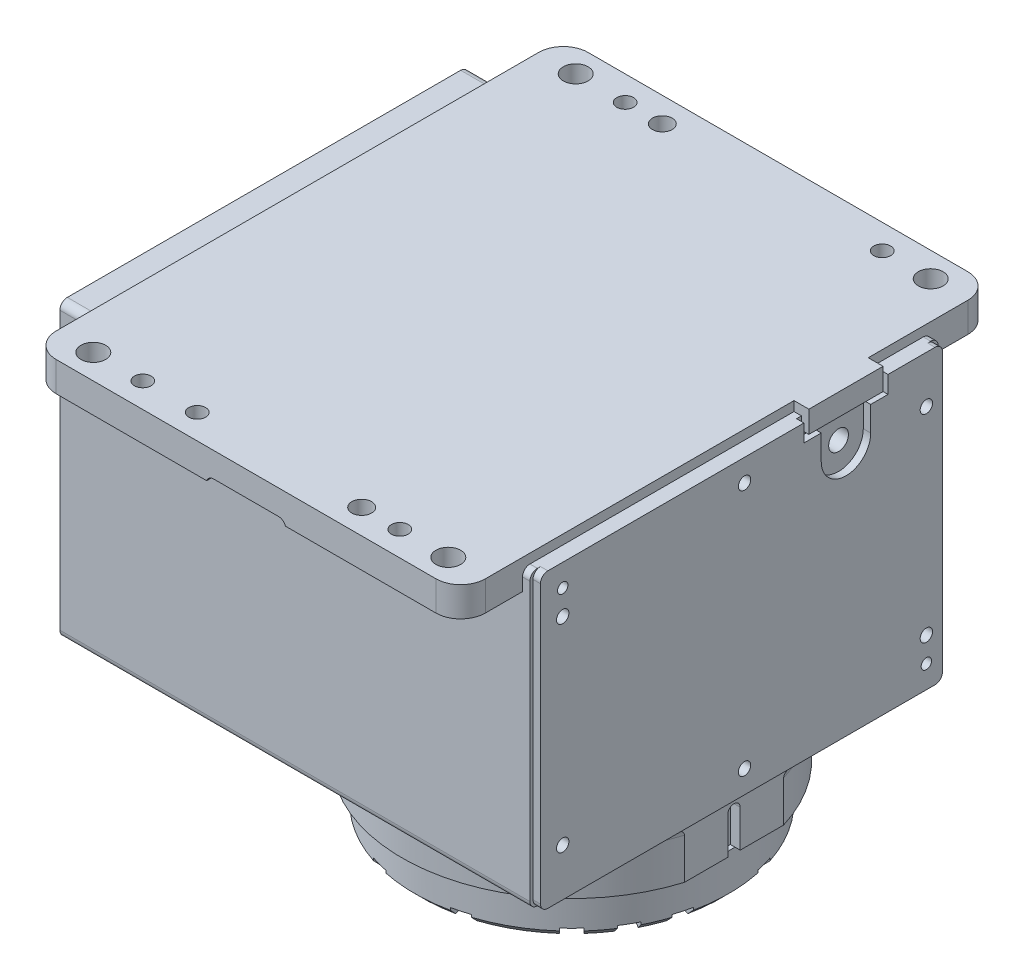
SolidWorks part; units mm, degrees
material "鋳合金鋼"
ref_plane "正面" through (0, 0, 0) normal (0, 0, 1) x (1, 0, 0)
ref_plane "平面" through (0, 0, 0) normal (0, 1, 0) x (1, 0, 0)
ref_plane "右側面" through (0, 0, 0) normal (1, 0, 0) x (0, 0, -1)
sketch "ｽｹｯﾁ1" plane through (0, 0, 0) normal (0, 1, 0) x (1, 0, 0)
  line L0 (0, 0) -> (0, 165)
  line L1 (0, 165) -> (187, 165)
  line L2 (187, 165) -> (187, 0)
  line L3 (187, 0) -> (0, 0)
extrude "ﾎﾞｽ - 押し出し1" add sketch "ｽｹｯﾁ1" along normal blind 118.0021 contours L1 L2 L3 L0
sketch "ｽｹｯﾁ2" plane through (0, 118.0021, 0) normal (0, 1, 0) x (1, 0, 0)
  line L0 (177, 190) -> (23.5, 190)
  line L1 (13.5, 180) -> (13.5, 165)
  line L2 (187, 165) -> (187, 180)
  line L3 (0, 165) -> (187, 165)
  line L4 (23.5, -25) -> (177, -25)
  line L5 (187, -15) -> (187, 0)
  line L6 (0, 0) -> (187, 0)
  line L7 (13.5, 0) -> (13.5, -15)
  arc A0 (23.5, 190) -> (13.5, 180) centre (23.5, 180) ccw
  arc A1 (187, 180) -> (177, 190) centre (177, 180) ccw
  circle A2 centre (28.5, 180) radius 5
  circle A3 centre (172, 180) radius 5
  circle A4 centre (48.5, 180) radius 3.4
  circle A5 centre (152.4024, 179.9985) radius 3.4
  circle A6 centre (63.5, 180) radius 4
  arc A7 (141, -15) -> (137, -19) centre (137, -15) cw
  arc A8 (177, -25) -> (187, -15) centre (177, -15) ccw
  arc A9 (13.5, -15) -> (23.5, -25) centre (23.5, -15) ccw
  circle A10 centre (28.5, -15) radius 5
  circle A11 centre (172, -15) radius 5
  circle A12 centre (70.5, -15) radius 3.4
  circle A13 centre (152.4025, -15) radius 3.4
  circle A14 centre (137, -15) radius 4
  circle A15 centre (48.5, -15) radius 3.4
  line M4 (187, 165) -> (0, 165)
extrude "ﾎﾞｽ - 押し出し2" add sketch "ｽｹｯﾁ2" against normal blind 8.0022 contours L2 A1 L0 A0 L1 A6 A5 A4 A3 A2 M4 | L7 A9 L4 A8 L5 L6 A15 A14 A7 A13 A12 A11 A10 region at (100.7065, 118.0021, -177.2159) region at (100.0536, 118.0021, 12.1905)
sketch "ｽｹｯﾁ5" plane through (0, 0, -190) normal (0, 0, -1) x (-1, 0, 0)
  line L0 (-84.3273, 118.0021) -> (-116.1727, 118.0021)
  line L1 (-116.1727, 118.0021) -> (-116.1727, 109.9999)
  line L2 (-177, 109.9999) -> (-23.5, 109.9999) construction
  line L3 (-116.1727, 109.9999) -> (-84.3273, 109.9999)
  line L4 (-84.3273, 109.9999) -> (-84.3273, 118.0021)
  line L5 (-100.25, 109.9999) -> (-100.25, 118.0021) construction
  line L6 (-113.3443, 111.9999) -> (-87.1557, 111.9999)
  line L7 (-84.3273, 109.9999) -> (-116.1727, 109.9999)
  arc A0 (-113.3443, 111.9999) -> (-116.1727, 109.9999) centre (-113.3443, 108.9999) ccw
  arc A1 (-87.1557, 111.9999) -> (-84.3273, 109.9999) centre (-87.1557, 108.9999) cw
  line M5 (-177, 109.9999) -> (-23.5, 109.9999)
extrude "ｶｯﾄ - 押し出し1" cut sketch "ｽｹｯﾁ5" against normal up to vertex (25 mm away) contours L5 L6 A0 M5 | L5 L7 A1 L6 region at (92.658, 110.9765, -190) region at (107.842, 110.9765, -190) up to point (187, 109.9999, -165)
sketch "ｽｹｯﾁ8" plane through (0, 0, 25) normal (0, 0, 1) x (1, 0, 0)
  line L0 (116.1727, 118.0021) -> (84.3273, 118.0021)
  line L1 (84.3273, 118.0021) -> (84.3273, 109.9999)
  line L2 (84.3273, 109.9999) -> (116.1727, 109.9999)
  line L3 (116.1727, 109.9999) -> (116.1727, 118.0021)
  line L4 (100.25, 109.9999) -> (100.25, 118.0021) construction
  line L5 (87.1557, 111.9999) -> (113.3443, 111.9999)
  line L6 (116.1727, 109.9999) -> (84.3273, 109.9999)
  line L7 (177, 109.9999) -> (23.5, 109.9999)
  line L8 (23.5, 109.9999) -> (177, 109.9999) construction
  arc A0 (87.1557, 111.9999) -> (84.3273, 109.9999) centre (87.1557, 108.9999) ccw
  arc A1 (113.3443, 111.9999) -> (116.1727, 109.9999) centre (113.3443, 108.9999) cw
  point P16 (100.25, 109.9999)
  line M3 (23.5, 109.9999) -> (177, 109.9999)
extrude "ｶｯﾄ - 押し出し2" cut sketch "ｽｹｯﾁ8" against normal up to vertex (25 mm away) contours L4 L7 A1 L5 | L4 L5 A0 M3 region at (107.842, 110.9765, 25) region at (92.658, 110.9765, 25) up to point (13.5, 109.9999, 0)
sketch "ｽｹｯﾁ11" plane through (0, 118.0021, 0) normal (0, 1, 0) x (1, 0, 0)
  line L0 (13.5, 165) -> (13.5, 0)
  line L1 (13.5, 0) -> (13.5, -15)
  line L2 (23.5, -25) -> (177, -25)
  line L3 (187, -15) -> (187, 180)
  line L4 (177, 190) -> (23.5, 190)
  line L5 (177, 190) -> (23.5, 190) construction
  line L6 (13.5, 180) -> (13.5, 165)
  arc A0 (187, 180) -> (177, 190) centre (177, 180) ccw construction
  arc A1 (23.5, 190) -> (13.5, 180) centre (23.5, 180) ccw
  arc A2 (13.5, -15) -> (23.5, -25) centre (23.5, -15) ccw
  arc A3 (177, -25) -> (187, -15) centre (177, -15) ccw
  arc A4 (177, 190) -> (187, 180) centre (177, 180) cw
  circle A5 centre (172, -15) radius 5
  circle A6 centre (152.4025, -15) radius 3.4
  circle A7 centre (137, -15) radius 4
  circle A8 centre (28.5, -15) radius 5
  circle A9 centre (48.5, -15) radius 3.4
  circle A10 centre (70.5, -15) radius 3.4
  circle A11 centre (172, 180) radius 5
  circle A12 centre (152.4024, 179.9985) radius 3.4
  circle A13 centre (63.5, 180) radius 4
  circle A14 centre (48.5, 180) radius 3.4
  circle A15 centre (28.5, 180) radius 5
extrude "ﾎﾞｽ - 押し出し4" add sketch "ｽｹｯﾁ11" along normal blind 3.9978
fillet "ﾌｨﾚｯﾄ1" radius 3 1 edges
sketch "ｽｹｯﾁ12" plane through (187, 0, 0) normal (1, 0, 0) x (0, 0, -1)
  line L0 (165, 0) -> (165, 121.9999)
  line L1 (-15, 121.9999) -> (180, 121.9999) construction
  line L2 (165, 121.9999) -> (0, 121.9999)
  line L3 (0, 121.9999) -> (0, 0)
  line L4 (0, 0) -> (165, 0)
  line L5 (165, 0) -> (167.2004, -1.5507)
  line M1 (0, 0) -> (165, 0)
  line M2 (165, 0) -> (165, 109.9999)
  line M5 (180, 121.9999) -> (-15, 121.9999)
  line M8 (0, 109.9999) -> (0, 0)
extrude "ﾎﾞｽ - 押し出し5" add sketch "ｽｹｯﾁ12" along normal blind 3 contours L3 L0 M5 M8 M1 M2 region at (187, 60.9999, -82.5)
sketch "ｽｹｯﾁ14" plane through (190, 0, 0) normal (1, 0, 0) x (0, 0, -1)
  line L1 (160.75, 0) -> (4.25, 0)
  line L2 (0, 0) -> (165, 0) construction
  line L3 (163.75, 3) -> (163.75, 118.9999)
  line L4 (165, 121.9999) -> (0, 121.9999) construction
  line L5 (160.75, 121.9999) -> (4.25, 121.9999)
  line L6 (1.25, 118.9999) -> (1.25, 3)
  arc A0 (4.25, 121.9999) -> (1.25, 118.9999) centre (4.25, 118.9999) ccw
  arc A1 (163.75, 118.9999) -> (160.75, 121.9999) centre (160.75, 118.9999) ccw
  arc A2 (4.25, 0) -> (1.25, 3) centre (4.25, 3) cw
  arc A3 (160.75, 0) -> (163.75, 3) centre (160.75, 3) ccw
  point P4 (82.5, 0)
  point P11 (1.25, 121.9999)
  point P14 (163.75, 121.9999)
  dimension "D1" = 3
extrude "ﾎﾞｽ - 押し出し7" add sketch "ｽｹｯﾁ14" along normal blind 3
sketch "ｽｹｯﾁ16" plane through (193, 0, 0) normal (1, 0, 0) x (0, 0, -1)
  line L0 (109.9001, 121.9999) -> (109.9001, 118.157)
  line L1 (109.9001, 118.157) -> (1.25, 118.157)
  line L2 (149.75, 121.9999) -> (149.75, 109.9999)
  line L3 (160.75, 121.9999) -> (4.25, 121.9999) construction
  line L4 (109.9001, 118.157) -> (163.75, 118.157)
  line L5 (117.75, 109.9999) -> (117.75, 121.9999)
  line L6 (117.75, 121.9999) -> (149.75, 121.9999)
  line L7 (163.75, 3) -> (163.75, 118.9999) construction
  line L8 (1.25, 118.9999) -> (1.25, 3) construction
  line L9 (1.25, 118.157) -> (1.25, 118.9999)
  line L10 (1.25, 118.9999) -> (1.25, 121.9999)
  line L11 (1.25, 121.9999) -> (163.75, 121.9999)
  line L12 (163.75, 121.9999) -> (163.75, 118.157)
  arc A0 (149.75, 109.9999) -> (117.75, 109.9999) centre (133.75, 109.9999) cw
  arc M8 (4.25, 121.9999) -> (1.25, 118.9999) centre (4.25, 118.9999) ccw
  line M9 (1.25, 118.9999) -> (1.25, 3)
  line M13 (163.75, 3) -> (163.75, 118.9999)
  arc M14 (163.75, 118.9999) -> (160.75, 121.9999) centre (160.75, 118.9999) ccw
  line M15 (160.75, 121.9999) -> (4.25, 121.9999)
extrude "ｶｯﾄ - 押し出し3" cut sketch "ｽｹｯﾁ16" against normal blind 3 contours L1 L0 M15 M8 M9 | L4 L5 L0 M15 | L5 L4 L2 M15 | L2 L4 M13 M14 M15 | L12 L11 M14 | L11 L10 M8 region at (193, 120.0784, -113.8251) region at (193, 120.0726, -55.8244) region at (193, 121.3298, -1.9201) region at (193, 120.0784, -133.75) region at (193, 120.0318, -156.5143) region at (193, 121.3298, -163.0799)
sketch "ｽｹｯﾁ17" plane through (190, 0, 0) normal (1, 0, 0) x (0, 0, -1)
  line L0 (1.25, 118.157) -> (0, 118.157)
  line L1 (0, 121.9999) -> (0, 0) construction
  line L2 (0, 118.157) -> (165, 118.157)
  line L3 (165, 0) -> (165, 121.9999) construction
  line L4 (165, 118.157) -> (165, 121.9999)
  line L5 (0, 118.157) -> (0, 121.9999)
  line L6 (165, 121.9999) -> (0, 121.9999) construction
  line L7 (0, 121.9999) -> (165, 121.9999)
  line M1 (165, 121.9999) -> (0, 121.9999)
  line M2 (0, 121.9999) -> (0, 0)
  line M6 (1.25, 118.157) -> (163.75, 118.157)
  line M10 (165, 0) -> (165, 121.9999)
extrude "ｶｯﾄ - 押し出し4" cut sketch "ｽｹｯﾁ17" against normal blind 3 contours L2 L0 M6 M10 M1 M2 region at (190, 120.0784, -82.5)
fillet "ﾌｨﾚｯﾄ2" radius 3 2 edges at (191.5, 118.157, -163.75) (191.5, 118.157, -1.25)
fillet "ﾌｨﾚｯﾄ3" radius 3 2 edges at (188.5, 118.157, -165) (188.5, 118.157, 0)
fillet "ﾌｨﾚｯﾄ4" radius 3 2 edges at (95, 0, -165) (95, 0, 0)
sketch "ｽｹｯﾁ26" plane through (193, 0, 0) normal (1, 0, 0) x (0, 0, -1)
  line L0 (134.75, 118.157) -> (134.75, 111.157)
  line L2 (124.75, 91.157) -> (124.75, 101.157)
  line L3 (160.75, 118.157) -> (4.25, 118.157) construction
  line L4 (134.75, 111.157) -> (141.75, 111.157)
  line L5 (141.75, 111.157) -> (141.75, 118.157)
  line L6 (141.75, 118.157) -> (134.75, 118.157)
  line L7 (124.75, 118.157) -> (124.75, 91.157)
  line L8 (134.75, 101.157) -> (134.75, 118.157)
  line L9 (114.75, 101.157) -> (114.75, 118.157)
  line L10 (114.75, 111.157) -> (107.75, 111.157)
  line L11 (107.75, 111.157) -> (107.75, 118.157)
  line L12 (107.75, 118.157) -> (114.75, 118.157)
  line L13 (141.75, 118.157) -> (134.75, 118.157)
  line L14 (134.75, 118.157) -> (114.75, 118.157)
  arc A0 (134.75, 101.157) -> (114.75, 101.157) centre (124.75, 101.157) cw
  line M6 (160.75, 118.157) -> (4.25, 118.157)
extrude "ｶｯﾄ - 押し出し9" cut sketch "ｽｹｯﾁ26" against normal blind 3 contours A0 L8 L0 L7 L2 M6 | A0 L2 L7 L9 M6 region at (193, 105.6298, -129.5111) region at (193, 105.6298, -119.9889)
extrude "ｶｯﾄ - 押し出し10" cut sketch "ｽｹｯﾁ26<4>" against normal blind 6 contours L11 L10 L9 M6 | L4 L5 L0 M6 region at (193, 114.657, -138.25) region at (193, 114.657, -111.25)
sketch "ｽｹｯﾁ26<4>" plane through (193, 0, 0) normal (1, 0, 0) x (0, 0, -1) same geometry as "ｽｹｯﾁ26"
sketch "ｽｹｯﾁ27" plane through (190, 0, 0) normal (1, 0, 0) x (0, 0, -1)
  line L1 (134.75, 111.157) -> (134.75, 118.157) construction
  line L2 (134.75, 113.157) -> (114.75, 113.157)
  line L3 (114.75, 111.157) -> (114.75, 118.157) construction
  line L4 (114.75, 113.157) -> (114.75, 118.157)
  line L5 (114.75, 118.157) -> (134.75, 118.157)
  line L6 (134.75, 118.157) -> (134.75, 113.157)
extrude "ｶｯﾄ - 押し出し11" cut sketch "ｽｹｯﾁ27" against normal blind 3
sketch "ｽｹｯﾁ28" plane through (187, 0, 0) normal (1, 0, 0) x (0, 0, -1)
  line L0 (134.75, 113.157) -> (139.75, 113.157)
  line L1 (139.75, 113.157) -> (139.75, 121.9999)
  line L2 (-15, 121.9999) -> (180, 121.9999) construction
  line L3 (109.75, 121.9999) -> (139.75, 121.9999)
  line L4 (114.75, 113.157) -> (109.75, 113.157)
  line L5 (109.75, 113.157) -> (109.75, 121.9999)
  line L6 (134.75, 113.157) -> (114.75, 113.157)
extrude "ﾎﾞｽ - 押し出し11" add sketch "ｽｹｯﾁ28" along normal blind 6
sketch "ｽｹｯﾁ29" plane through (187, 0, 0) normal (1, 0, 0) x (0, 0, -1)
  line L0 (141.75, 118.157) -> (139.75, 118.157)
  line L1 (139.75, 113.157) -> (139.75, 121.9999) construction
  line L2 (139.75, 118.157) -> (139.75, 113.157)
  line L3 (139.75, 113.157) -> (134.75, 113.157)
  line L4 (134.75, 113.157) -> (134.75, 111.157)
  line L5 (134.75, 111.157) -> (141.75, 111.157)
  line L6 (141.75, 111.157) -> (141.75, 118.157)
  line L7 (124.75, 101.157) -> (124.75, 122.2227) construction
  line L8 (107.75, 111.157) -> (107.75, 118.157)
  line L9 (114.75, 111.157) -> (107.75, 111.157)
  line L10 (114.75, 113.157) -> (114.75, 111.157)
  line L11 (109.75, 113.157) -> (114.75, 113.157)
  line L12 (109.75, 118.157) -> (109.75, 113.157)
  line L13 (107.75, 118.157) -> (109.75, 118.157)
extrude "ﾎﾞｽ - 押し出し12" add sketch "ｽｹｯﾁ29" along normal blind 3
sketch "ｽｹｯﾁ30" plane through (190, 0, 0) normal (1, 0, 0) x (0, 0, -1)
  line L0 (124.75, 113.157) -> (124.75, 91.157) construction
  line L1 (109.75, 113.157) -> (139.75, 113.157) construction
  arc A0 (114.75, 101.157) -> (134.75, 101.157) centre (124.75, 101.157) ccw construction
  circle A3 centre (124.75, 102.157) radius 4
  point P7 (124.75, 102.157)
sketch "ｽｹｯﾁ32" plane through (0, 0, 0) normal (0, -1, 0) x (1, 0, 0)
  line L0 (193, -82.5) -> (55.8246, -82.5)
  line L1 (193, -4.25) -> (193, -160.75) construction
  circle A0 centre (124.4123, -82.5) radius 68.5877
extrude "ﾎﾞｽ - 押し出し18" add sketch "ｽｹｯﾁ32" along normal blind 21.5 contours L0 A0 | L0 A0 region at (124.4123, 0, -111.6095) region at (124.4123, 0, -53.3905)
sketch "ｽｹｯﾁ35" plane through (0, -21.5, 0) normal (0, -1, 0) x (1, 0, 0)
  line L0 (193, -82.5) -> (190, -82.5)
  line L1 (190, -82.5) -> (190, -49.1415)
  line L2 (190, -49.1415) -> (190, -119.937)
  line L3 (193, -119.937) -> (193, -49.1415)
  line L4 (193, -49.1415) -> (190, -49.1415)
  circle A0 centre (124.4123, -82.5) radius 68.5877 construction
  circle M1 centre (124.4123, -82.5) radius 68.5877
extrude "ｶｯﾄ - 押し出し18" cut sketch "ｽｹｯﾁ35" against normal blind 21.5 contours L1 L0 M1 | L0 L2 M1 region at (191.2023, -21.5, -90.0461) region at (191.2023, -21.5, -74.9539)
fillet "ﾌｨﾚｯﾄ7" radius 5 1 edges at (55.8246, 0, -82.5)
sketch "ｽｹｯﾁ36" plane through (190, 0, 0) normal (1, 0, 0) x (0, 0, -1)
  line L0 (82.5, -21.5) -> (82.5, -6.5)
  line L1 (102.5631, -21.5) -> (62.4369, -21.5) construction
  line L2 (80, -6.5) -> (80, -21.5)
  line L3 (80, -21.5) -> (85, -21.5)
  line L4 (85, -21.5) -> (85, -6.5)
  arc A0 (80, -6.5) -> (85, -6.5) centre (82.5, -6.5) cw
  line M2 (62.4369, -21.5) -> (102.5631, -21.5)
extrude "ｶｯﾄ - 押し出し19" cut sketch "ｽｹｯﾁ36" against normal blind 4 contours A0 L2 L4 M2 region at (190, -4.182, -82.5)
sketch "ｽｹｯﾁ37" plane through (0, -21.5, 0) normal (0, -1, 0) x (-1, 0, 0)
  line L0 (-124.4123, 82.5) -> (-60.9123, 82.5)
  circle A0 centre (-124.4123, 82.5) radius 63.5
  line M1 (-190, 85) -> (-186, 85)
  line M2 (-186, 85) -> (-186, 80)
  line M3 (-186, 80) -> (-190, 80)
extrude "ﾎﾞｽ - 押し出し19" add sketch "ｽｹｯﾁ37" along normal blind 18 contours A0 M3 M1 M2 | A0 M1 M3 M2 region at (123.1974, -21.5, -20.8077) region at (186.948, -21.5, -82.5)
chamfer "面取り3" distance 3 distance2 3 1 edges at (124.4123, -39.5, -146)
sketch "ｽｹｯﾁ38" plane through (0, -39.5, 0) normal (0, -1, 0) x (1, 0, 0)
  line L0 (62.1702, -69.4457) -> (63.9819, -62.6843)
  line L1 (63.9819, -102.3157) -> (62.1702, -95.5543)
  line L2 (63.9819, -62.6843) -> (71.2263, -64.6254)
  line L3 (62.1702, -95.5543) -> (69.4146, -93.6131)
  line L4 (69.4146, -93.6131) -> (71.2263, -100.3746)
  line L5 (71.2263, -100.3746) -> (63.9819, -102.3157)
  line L6 (71.2263, -64.6254) -> (69.4146, -71.3869)
  line L7 (69.4146, -71.3869) -> (62.1702, -69.4457)
  line L8 (77.0362, -40.0736) -> (81.9859, -35.1238)
  line L9 (81.9859, -35.1238) -> (87.2892, -40.4271)
  line L10 (87.2892, -40.4271) -> (82.3395, -45.3769)
  line L11 (82.3395, -45.3769) -> (77.0362, -40.0736)
  line L12 (104.5966, -22.0696) -> (111.358, -20.2578)
  line L13 (111.358, -20.2578) -> (113.2992, -27.5023)
  line L14 (113.2992, -27.5023) -> (106.5377, -29.314)
  line L15 (106.5377, -29.314) -> (104.5966, -22.0696)
  line L16 (137.4666, -20.2578) -> (144.2281, -22.0696)
  line L17 (144.2281, -22.0696) -> (142.2869, -29.314)
  line L18 (142.2869, -29.314) -> (135.5254, -27.5023)
  line L19 (135.5254, -27.5023) -> (137.4666, -20.2578)
  line L20 (166.8387, -35.1238) -> (171.7885, -40.0736)
  line L21 (171.7885, -40.0736) -> (166.4852, -45.3769)
  line L22 (166.4852, -45.3769) -> (161.5354, -40.4271)
  line L23 (161.5354, -40.4271) -> (166.8387, -35.1238)
  line L24 (184.8427, -62.6843) -> (186.6545, -69.4457)
  line L25 (186.6545, -69.4457) -> (179.41, -71.3869)
  line L26 (179.41, -71.3869) -> (177.5983, -64.6254)
  line L27 (177.5983, -64.6254) -> (184.8427, -62.6843)
  line L28 (186.6545, -95.5543) -> (184.8427, -102.3157)
  line L29 (184.8427, -102.3157) -> (177.5983, -100.3746)
  line L30 (177.5983, -100.3746) -> (179.41, -93.6131)
  line L31 (179.41, -93.6131) -> (186.6545, -95.5543)
  line L32 (171.7885, -124.9264) -> (166.8387, -129.8762)
  line L33 (166.8387, -129.8762) -> (161.5354, -124.5729)
  line L34 (161.5354, -124.5729) -> (166.4852, -119.6231)
  line L35 (166.4852, -119.6231) -> (171.7885, -124.9264)
  line L36 (144.2281, -142.9304) -> (137.4666, -144.7422)
  line L37 (137.4666, -144.7422) -> (135.5254, -137.4977)
  line L38 (135.5254, -137.4977) -> (142.2869, -135.686)
  line L39 (142.2869, -135.686) -> (144.2281, -142.9304)
  line L40 (111.358, -144.7422) -> (104.5966, -142.9304)
  line L41 (104.5966, -142.9304) -> (106.5377, -135.686)
  line L42 (106.5377, -135.686) -> (113.2992, -137.4977)
  line L43 (113.2992, -137.4977) -> (111.358, -144.7422)
  line L44 (81.9859, -129.8762) -> (77.0362, -124.9264)
  line L45 (77.0362, -124.9264) -> (82.3395, -119.6231)
  line L46 (82.3395, -119.6231) -> (87.2892, -124.5729)
  line L47 (87.2892, -124.5729) -> (81.9859, -129.8762)
  line L48 (71.1697, -117.2811) -> (67.6697, -111.2189)
  line L49 (177.6549, -47.7189) -> (181.1549, -53.7811)
  line L50 (181.1549, -53.7811) -> (175.0927, -57.2811)
  line L51 (67.6697, -111.2189) -> (73.7319, -107.7189)
  line L52 (73.7319, -107.7189) -> (77.2319, -113.7811)
  line L53 (77.2319, -113.7811) -> (71.1697, -117.2811)
  line L54 (175.0927, -57.2811) -> (171.5927, -51.2189)
  line L55 (171.5927, -51.2189) -> (177.6549, -47.7189)
  point P0 (124.4123, -82.5)
  point P52 (124.4123, -82.5)
  point P62 (124.4123, -82.5)
  dimension "D1" = 12
  dimension "D2" = 2
extrude "ｶｯﾄ - 押し出し20" cut sketch "ｽｹｯﾁ38" against normal blind 4
sketch "ｽｹｯﾁ39" plane through (0, -35.5, 0) normal (0, -1, 0) x (1, 0, 0)
  circle A1 centre (182.1264, -97.9644) radius 1.5
  circle A2 centre (166.6619, -124.7496) radius 1.5
  circle A3 centre (139.8768, -140.2141) radius 1.5
  circle A4 centre (108.9479, -140.2141) radius 1.5
  circle A5 centre (82.1627, -124.7496) radius 1.5
  circle A6 centre (66.6982, -97.9644) radius 1.5
  circle A7 centre (66.6982, -67.0356) radius 1.5
  circle A8 centre (82.1627, -40.2504) radius 1.5
  circle A9 centre (108.9479, -24.7859) radius 1.5
  circle A10 centre (139.8768, -24.7859) radius 1.5
  circle A11 centre (166.6619, -40.2504) radius 1.5
  circle A12 centre (182.1264, -67.0356) radius 1.5
  circle A14 centre (176.3738, -52.5) radius 1.5
  circle A15 centre (72.4508, -112.5) radius 1.5
  point P0 (124.4123, -82.5)
  point P28 (124.4123, -82.5)
  point P31 (124.4123, -82.5)
  dimension "D1" = 12
  dimension "D2" = 2
extrude "ｶｯﾄ - 押し出し27" cut sketch "ｽｹｯﾁ39" against normal blind 6
extrude "ｶｯﾄ - 押し出し29" cut sketch "ｽｹｯﾁ30" against normal blind 6
sketch "ｽｹｯﾁ40" plane through (193, 0, 0) normal (1, 0, 0) x (0, 0, -1)
  circle A0 centre (10.25, 109.157) radius 2.1
  circle A1 centre (157.2453, 9.157) radius 2.1
  circle A8 centre (157.2453, 99.157) radius 2.5
  circle A9 centre (83.7453, 109.157) radius 2.5
  circle A10 centre (10.25, 99.157) radius 2.5
  circle A11 centre (10.25, 19.157) radius 2.5
  circle A12 centre (83.7453, 9.157) radius 2.5
  circle A13 centre (157.2453, 19.157) radius 2.5
  point P1 (10.25, 109.157)
extrude "ｶｯﾄ - 押し出し30" cut sketch "ｽｹｯﾁ40" against normal blind 8
sketch "ｽｹｯﾁ41" plane through (0, 0, 0) normal (-1, 0, 0) x (0, 0, 1)
  line L0 (-82.5, 118.0021) -> (-82.5, 0) construction
  line L1 (0, 118.0021) -> (-165, 118.0021) construction
  line L2 (-3, 0) -> (-162, 0) construction
  line L3 (-165, 60.5011) -> (0, 60.5011) construction
  line L4 (-165, 118.0021) -> (-165, 3) construction
  line L5 (0, 118.0021) -> (0, 3) construction
  circle A0 centre (-82.5, 109.0021) radius 2.5
  circle A1 centre (-156, 99.0021) radius 2.5
  circle A2 centre (-156, 22) radius 2.5
  circle A3 centre (-82.5, 12) radius 2.5
  circle A4 centre (-9, 99.0021) radius 2.5
  circle A5 centre (-9, 22) radius 2.5
extrude "ｶｯﾄ - 押し出し31" cut sketch "ｽｹｯﾁ41" against normal blind 8
sketch "ｽｹｯﾁ42" plane through (0, -39.5, 0) normal (0, -1, 0) x (1, 0, 0)
  circle A0 centre (124.4123, -82.5) radius 55
extrude "ｶｯﾄ - 押し出し32" cut sketch "ｽｹｯﾁ42" against normal blind 10
fillet "ﾌｨﾚｯﾄ8" radius 3 4 edges at (12.6213, 118.8808, -165) (12.6213, 118.8808, 0)
